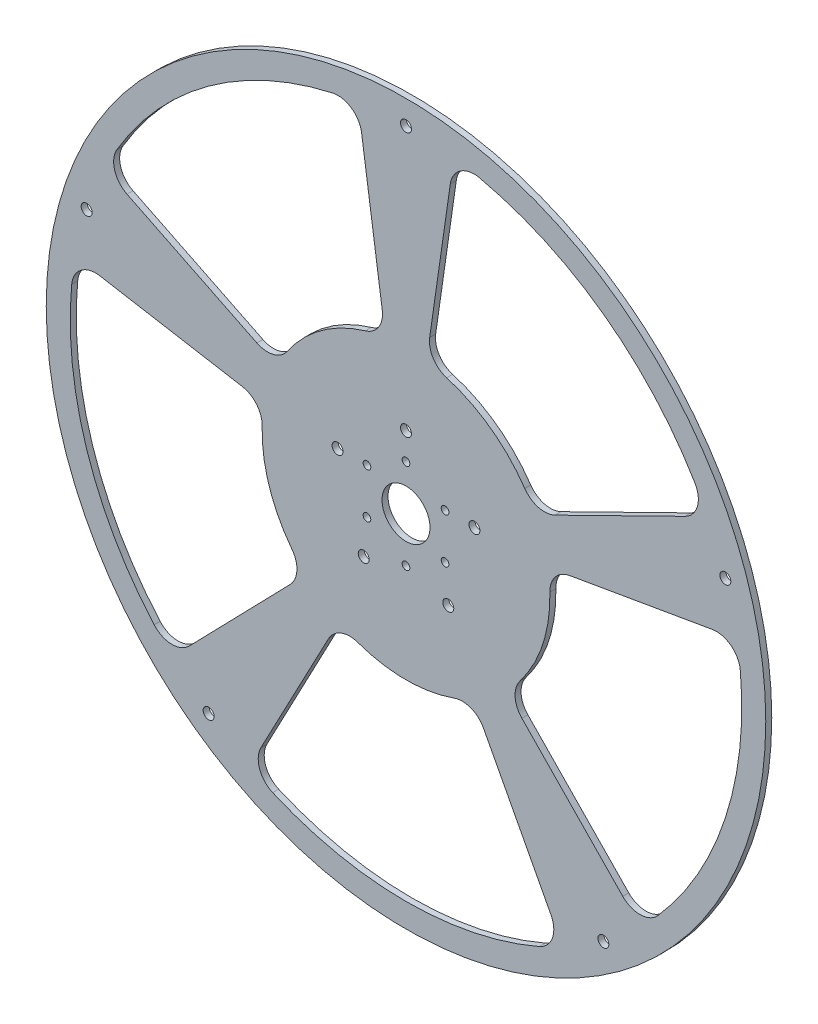
SolidWorks part; units mm, degrees
material "6061 Alloy"
ref_plane "Front Plane" through (0, 0, 0) normal (0, 0, 1) x (1, 0, 0)
ref_plane "Top Plane" through (0, 0, 0) normal (0, 1, 0) x (1, 0, 0)
ref_plane "Right Plane" through (0, 0, 0) normal (1, 0, 0) x (0, 0, -1)
sketch "Sketch1" plane through (0, 0, 0) normal (0, 0, 1) x (1, 0, 0)
  line L0 (0, 177.8) -> (0, 0) construction
  line L1 (0, 0) -> (169.0978, 54.9432) construction
  line L2 (-169.0978, 54.9432) -> (0, 0) construction
  line L3 (0, 0) -> (-104.5082, -143.8432) construction
  line L4 (0, 0) -> (104.5082, -143.8432) construction
  line L5 (25.3351, 175.9857) -> (10.8579, 75.4224)
  line L6 (-25.4, 175.9764) -> (-10.8857, 75.4184)
  line L7 (68.3757, 33.6333) -> (159.5434, 78.4777)
  line L8 (75.0863, 12.9803) -> (175.2013, 30.2874)
  line L9 (53.1164, -54.6359) -> (123.9384, -127.4838)
  line L10 (35.548, -67.4002) -> (82.9453, -157.267)
  line L11 (-159.5434, 78.4777) -> (-68.3757, 33.6333)
  line L12 (-175.2013, 30.2874) -> (-75.0863, 12.9803)
  line L13 (-82.9453, -157.267) -> (-35.548, -67.4002)
  line L14 (-123.9384, -127.4838) -> (-53.1164, -54.6359)
  line L15 (0, 0) -> (-8.0097, 4.6244) construction
  line L16 (-8.0097, 4.6244) -> (-8.0097, -4.6244) construction
  line L17 (-8.0097, -4.6244) -> (0, -9.2488) construction
  line L18 (0, -9.2488) -> (8.0097, -4.6244) construction
  line L19 (8.0097, -4.6244) -> (8.0097, 4.6244) construction
  line L20 (8.0097, 4.6244) -> (0, 9.2488) construction
  line L21 (0, 9.2488) -> (-8.0097, 4.6244) construction
  line L22 (-8.0097, 4.6244) -> (-20.6772, 11.938) construction
  line L23 (0, 0) -> (0, 9.2488) construction
  line L24 (0, 9.2488) -> (0, 23.876) construction
  line L25 (0, 0) -> (8.0097, 4.6244) construction
  line L26 (8.0097, 4.6244) -> (20.6772, 11.938) construction
  line L27 (0, 0) -> (8.0097, -4.6244) construction
  line L28 (8.0097, -4.6244) -> (20.6772, -11.938) construction
  line L29 (0, 0) -> (0, -9.2488) construction
  line L30 (0, -9.2488) -> (0, -23.876) construction
  line L31 (0, 0) -> (-8.0097, -4.6244) construction
  line L32 (-8.0097, -4.6244) -> (-20.6772, -11.938) construction
  circle A0 centre (0, 0) radius 190.5
  arc A1 (-10.8857, 75.4184) -> (-68.3757, 33.6333) centre (0, 0) ccw
  arc A2 (-25.4, 175.9764) -> (-159.5434, 78.4777) centre (0, 0) ccw
  arc A3 (68.3757, 33.6333) -> (10.8579, 75.4224) centre (0, 0) ccw
  arc A4 (-75.0863, 12.9803) -> (-53.1164, -54.6359) centre (0, 0) ccw
  arc A5 (53.1164, -54.6359) -> (75.0863, 12.9803) centre (0, 0) ccw
  arc A6 (-35.548, -67.4002) -> (35.548, -67.4002) centre (0, 0) ccw
  arc A7 (159.5434, 78.4777) -> (25.3351, 175.9857) centre (0, 0) ccw
  arc A8 (123.9384, -127.4838) -> (175.2013, 30.2874) centre (0, 0) ccw
  arc A9 (-82.9453, -157.267) -> (82.9453, -157.267) centre (0, 0) ccw
  arc A10 (-175.2013, 30.2874) -> (-123.9384, -127.4838) centre (0, 0) ccw
  circle A11 centre (0, 0) radius 76.2 construction
  circle A12 centre (0, 0) radius 177.8 construction
  circle A13 centre (0, 0) radius 12.7
  circle A14 centre (-36.2353, 11.7735) radius 2.9
  circle A15 centre (-22.3946, -30.8235) radius 2.9
  circle A16 centre (22.3946, -30.8235) radius 2.9
  circle A17 centre (36.2353, 11.7735) radius 2.9
  circle A18 centre (0, 38.1) radius 2.9
  circle A19 centre (-169.0978, 54.9432) radius 2.9
  circle A20 centre (0, 177.8) radius 2.9
  circle A21 centre (169.0978, 54.9432) radius 2.9
  circle A22 centre (104.5082, -143.8432) radius 2.9
  circle A23 centre (-104.5082, -143.8432) radius 2.9
  circle A24 centre (0, 0) radius 8.0097 construction
  circle A25 centre (-20.6772, 11.938) radius 2.032
  circle A26 centre (0, 23.876) radius 2.032
  circle A27 centre (20.6772, 11.938) radius 2.032
  circle A28 centre (20.6772, -11.938) radius 2.032
  circle A29 centre (0, -23.876) radius 2.032
  circle A30 centre (-20.6772, -11.938) radius 2.032
  point P55 (0, 0)
  point P77 (0, 0)
  dimension "D1" = 381
  dimension "D2" = 152.4
  dimension "D3" = 355.6
  dimension "D22" = 25.4
  dimension "D23" = 5.8
  dimension "D24" = 5.8
  dimension "D25" = 5.8
  dimension "D26" = 5.8
  dimension "D27" = 5.8
  dimension "D33" = 5.8
  dimension "D36" = 4.064
  dimension "D4" = 72
  dimension "D5" = 72
  dimension "D6" = 72
  dimension "D7" = 72
  dimension "D8" = 25.4
  dimension "D9" = 25.4
  dimension "D10" = 25.4
  dimension "D11" = 25.4
  dimension "D12" = 25.4
  dimension "D13" = 25.4
  dimension "D14" = 25.4
  dimension "D15" = 25.4
  dimension "D16" = 25.4
  dimension "D17" = 25.4
  dimension "D18" = 21.7158
  dimension "D19" = 50.6702
  dimension "D20" = 50.6702
  dimension "D21" = 50.7351
  dimension "D28" = 38.1
  dimension "D29" = 38.1
  dimension "D30" = 38.1
  dimension "D31" = 38.1
  dimension "D32" = 38.1
  dimension "D35" = 23.876
  dimension "D34" = 5
  dimension "D37" = 6
extrude "Boss-Extrude3" add sketch "Sketch1" along normal blind 3.175
fillet "Fillet1" radius 12.7 1 edges at (-175.2013, 30.2874, 1.5875)
fillet "Fillet2" radius 12.7 13 edges at (35.548, -67.4002, 1.5875) (123.9384, -127.4838, 1.5875) (53.1164, -54.6359, 1.5875) (75.0863, 12.9803, 1.5875) (175.2013, 30.2874, 1.5875) (68.3757, 33.6333, 1.5875) (159.5434, 78.4777, 1.5875) (25.3351, 175.9857, 1.5875) (10.8579, 75.4224, 1.5875) (-10.8857, 75.4184, 1.5875) (-68.3757, 33.6333, 1.5875) (-25.4, 175.9764, 1.5875) (-159.5434, 78.4777, 1.5875)
fillet "Fillet3" radius 12.7 6 edges at (-75.0863, 12.9803, 1.5875) (-123.9384, -127.4838, 1.5875) (-53.1164, -54.6359, 1.5875) (82.9453, -157.267, 1.5875) (-82.9453, -157.267, 1.5875) (-35.548, -67.4002, 1.5875)
